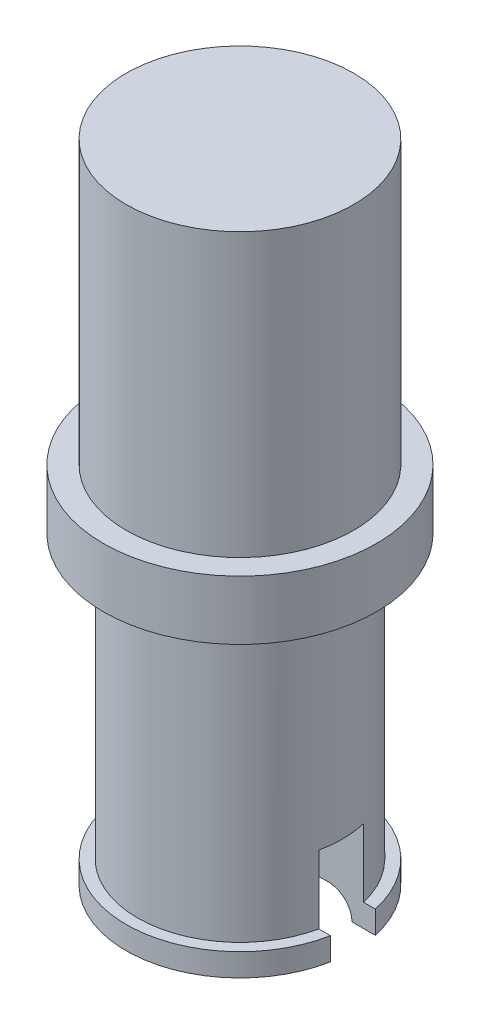
SolidWorks part; units mm, degrees
ref_plane "Front Plane" through (0, 0, 0) normal (0, 0, 1) x (1, 0, 0)
ref_plane "Top Plane" through (0, 0, 0) normal (0, 1, 0) x (1, 0, 0)
ref_plane "Right Plane" through (0, 0, 0) normal (1, 0, 0) x (0, 0, -1)
sketch "Sketch1" plane through (0, 0, 0) normal (0, 1, 0) x (1, 0, 0)
  circle A0 centre (0, 0) radius 2.5
  circle A1 centre (0, 0) radius 2
  dimension "D1" = 5
  dimension "D2" = 4
extrude "Boss-Extrude1" add sketch "Sketch1" along normal blind 0.5
sketch "Sketch3" plane through (0, 0.5, 0) normal (0, 1, 0) x (1, 0, 0)
  circle A0 centre (0, 0) radius 2.25
  circle A1 centre (0, 0) radius 1.25
  dimension "D1" = 4.5
  dimension "D2" = 1
extrude "Boss-Extrude2" add sketch "Sketch3" along normal blind 6.2
sketch "Sketch5" plane through (0, 6.7, 0) normal (0, 1, 0) x (1, 0, 0)
  circle A0 centre (0, 0) radius 3
  dimension "D1" = 6
extrude "Boss-Extrude3" add sketch "Sketch5" along normal blind 1.3
sketch "Sketch6" plane through (0, 8, 0) normal (0, 1, 0) x (1, 0, 0)
  circle A0 centre (0, 0) radius 2.5
  dimension "D1" = 5
extrude "Boss-Extrude4" add sketch "Sketch6" along normal blind 6.2
sketch "Sketch24" plane through (0, 0, 0) normal (0, -1, 0) x (-1, 0, 0)
  line L9 (2.6075, -0.4685) -> (-2.6767, -0.4685)
  line L10 (2.6075, -0.4685) -> (2.6075, 0.5315)
  line L11 (2.6075, 0.5315) -> (-2.6767, 0.5315)
  line L12 (-2.6767, -0.4685) -> (-2.6767, 0.5315)
  dimension "D1" = 1
extrude "Cut-Extrude1" cut sketch "Sketch24" against normal blind 2
fillet "Fillet1" radius 0.5 2 edges at (0, 0.5, 2) (0, 0.5, -2)
